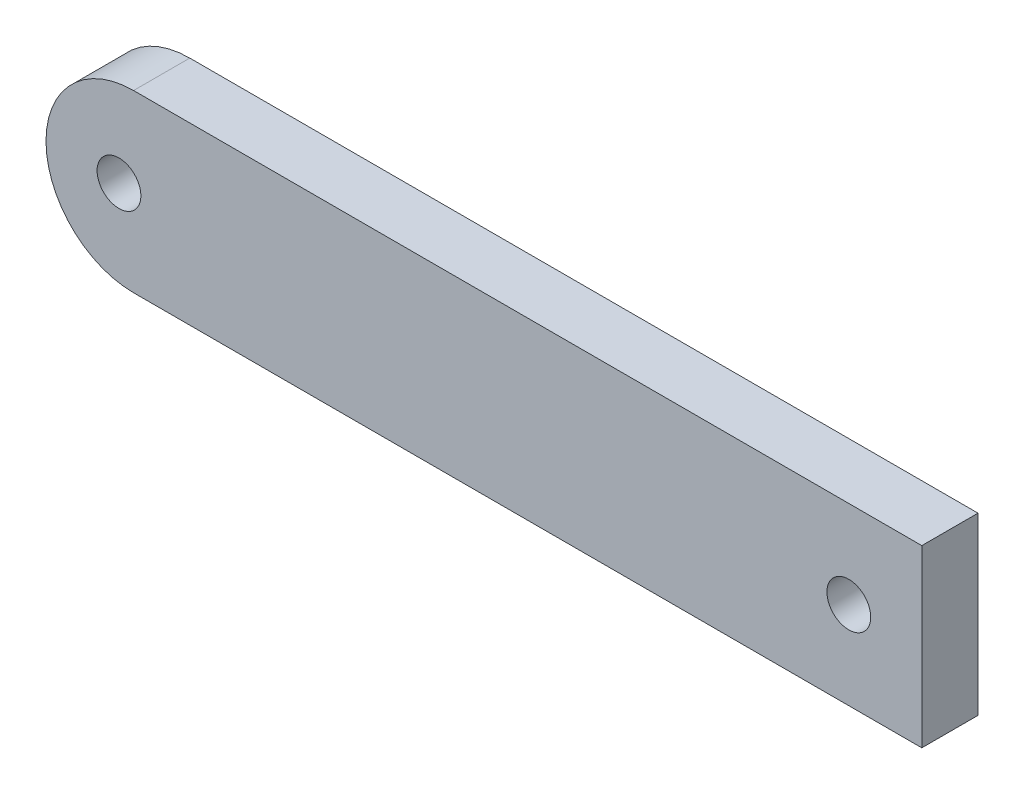
SolidWorks part; units mm, degrees
ref_plane "前视基准面" through (0, 0, 0) normal (0, 0, 1) x (1, 0, 0)
ref_plane "上视基准面" through (0, 0, 0) normal (0, 1, 0) x (1, 0, 0)
ref_plane "右视基准面" through (0, 0, 0) normal (1, 0, 0) x (0, 0, -1)
sketch "草图1" plane through (0, 0, 0) normal (0, 0, 1) x (1, 0, 0)
  line L1 (35, -6) -> (-25, -6)
  line L2 (35, -6) -> (35, 6)
  line L3 (35, 6) -> (-25, 6)
  line L4 (-25, -6) -> (-25, 6)
  circle A0 centre (-20, 0) radius 1.5
  circle A1 centre (30, 0) radius 1.5
  point P0 (0, 0)
extrude "凸台-拉伸1" add sketch "草图1" along normal blind 3.85
fillet "圆角1" radius 6 2 edges at (-25, -6, 1.925) (-25, 6, 1.925)
